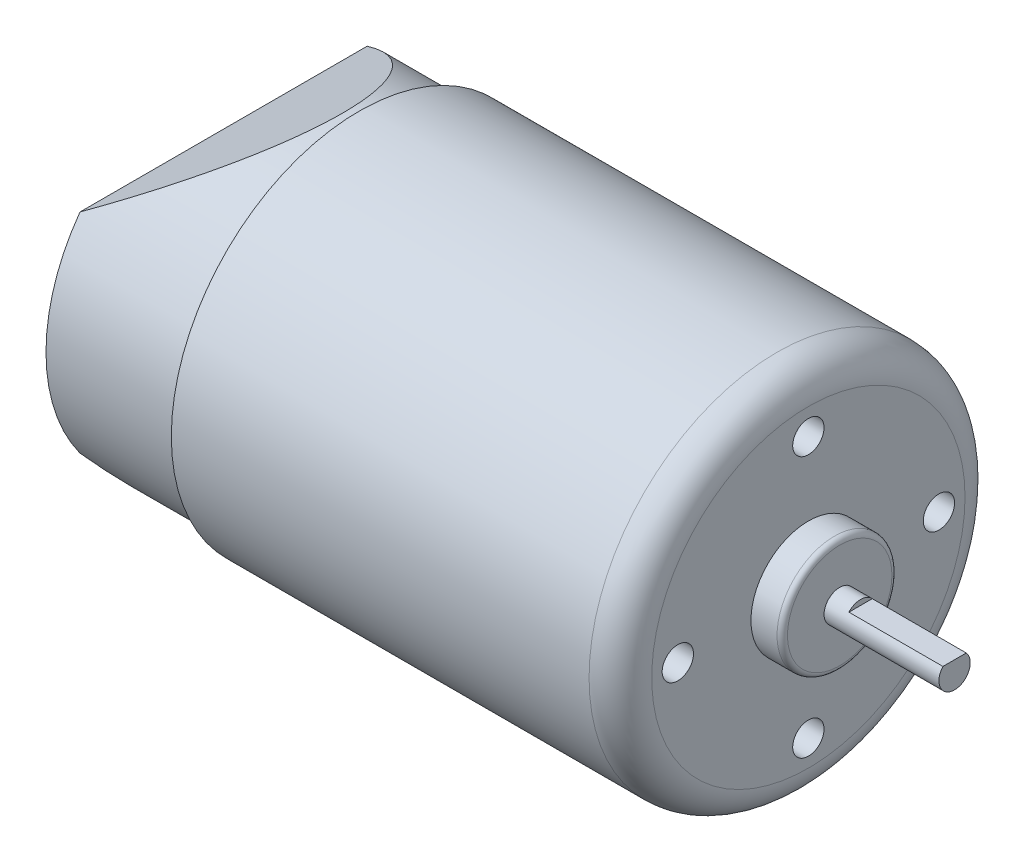
SolidWorks part; units mm, degrees
ref_plane "Front Plane" through (0, 0, 0) normal (0, 0, 1) x (1, 0, 0)
ref_plane "Top Plane" through (0, 0, 0) normal (0, 1, 0) x (1, 0, 0)
ref_plane "Right Plane" through (0, 0, 0) normal (1, 0, 0) x (0, 0, -1)
sketch "Sketch1" plane through (0, 0, 0) normal (1, 0, 0) x (0, 0, -1)
  circle A0 centre (0, 0) radius 18
  dimension "D1" = 36
extrude "Boss-Extrude1" add sketch "Sketch1" along normal blind 56
fillet "Fillet1" radius 3 1 edges at (56, 0, -18)
sketch "Sketch2" plane through (0, 0, 0) normal (0, 0, 1) x (1, 0, 0)
  line L0 (13, 18) -> (0, 10)
  line L1 (53, 18) -> (0, 18) construction
  line L2 (0, 18) -> (0, -18) construction
  line L3 (0, 10) -> (0, -10)
  line L4 (0, -10) -> (13, -18)
  line L5 (0, -18) -> (53, -18) construction
  line L6 (13, -18) -> (0, -18)
  line L7 (0, -18) -> (-7.8038, 17.2258)
  line L8 (-7.8038, 17.2258) -> (0, 18)
  line L9 (0, 18) -> (13, 18)
  dimension "D1" = 13
  dimension "D2" = 8
extrude "Cut-Extrude1" cut sketch "Sketch2" against normal up to surface and the other way up to surface up to face at (53, 0, -18) other way up to face at (53, 0, -18)
sketch "Sketch3" plane through (0, 0, 0) normal (0, 0, 1) x (1, 0, 0)
  line L0 (13, 18) -> (13, 17)
  line L1 (13, 17) -> (0, 17)
  line L2 (0, 17) -> (0, 18)
  line L3 (-7.8038, 17.2258) -> (0, 18) construction
  line L4 (0, 18) -> (13, 18)
  line L6 (0, 10) -> (0, -10) construction
  line L7 (-1000, 0) -> (49000, 0) construction
  dimension "D1" = 1
revolve "Cut-Revolve1" cut sketch "Sketch3" angle 360 about L7
sketch "Sketch4" plane through (56, 0, 0) normal (1, 0, 0) x (0, 0, -1)
  circle A0 centre (0, 0) radius 5.5
  dimension "D1" = 11
extrude "Boss-Extrude2" add sketch "Sketch4" along normal blind 3
fillet "Fillet2" radius 0.5 1 edges at (59, 0, -5.5)
sketch "Sketch5" plane through (59, 0, 0) normal (1, 0, 0) x (0, 0, -1)
  circle A0 centre (0, 0) radius 1.5
  dimension "D1" = 3
extrude "Boss-Extrude3" add sketch "Sketch5" along normal blind 11
sketch "Sketch6" plane through (0, 0, 0) normal (0, 0, 1) x (1, 0, 0)
  line L0 (70, 1.5) -> (70, 1)
  line L1 (70, -1.5) -> (70, 1.5) construction
  line L2 (70, 1) -> (61, 1)
  line L3 (61, 1) -> (61, 1.5)
  line L4 (70, 1.5) -> (59, 1.5) construction
  line L5 (61, 1.5) -> (70, 1.5)
  dimension "D1" = 9
  dimension "D2" = 0.5
extrude "Cut-Extrude2" cut sketch "Sketch6" against normal up to surface and the other way up to surface up to face at (70, 0, -1.5) other way up to face at (70, 0, -1.5)
sketch "Sketch7" plane through (56, 0, 0) normal (1, 0, 0) x (0, 0, -1)
  circle A0 centre (0, 12.5) radius 1.5
  circle A1 centre (0, 0) radius 5.5 construction
  circle A2 centre (12.5, 0) radius 1.5
  circle A3 centre (0, -12.5) radius 1.5
  circle A4 centre (-12.5, 0) radius 1.5
  dimension "D1" = 3
  dimension "D2" = 12.5
  dimension "D3" = 4
extrude "Cut-Extrude3" cut sketch "Sketch7" against normal blind 3
sketch "Sketch8" plane through (0, 0, 0) normal (0, 1, 0) x (1, 0, 0)
  line L0 (-1000, 0) -> (49000, 0) construction
  point P1 (-40, 0)
  dimension "D1" = 40
